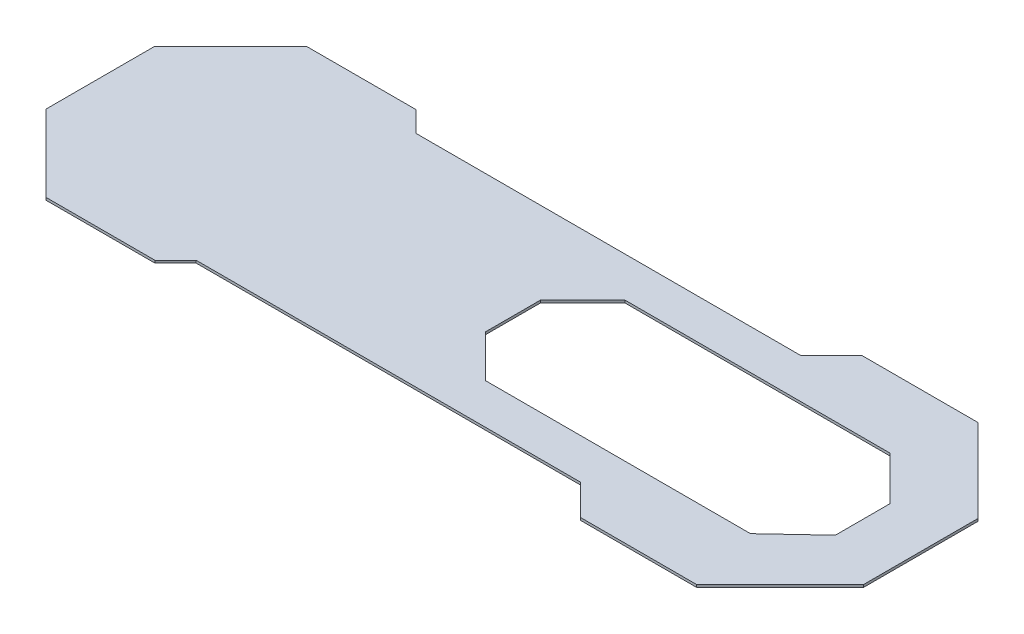
SolidWorks part; units mm, degrees
ref_plane "Спереди" through (0, 0, 0) normal (0, 0, 1) x (1, 0, 0)
ref_plane "Сверху" through (0, 0, 0) normal (0, 1, 0) x (1, 0, 0)
ref_plane "Справа" through (0, 0, 0) normal (1, 0, 0) x (0, 0, -1)
sketch "Эскиз1" plane through (0, 0, 0) normal (0, 1, 0) x (1, 0, 0)
  line L0 (-58.5138, -161.8896) -> (-212.3646, -161.8896)
  line L5 (-44.5996, -149.3896) -> (-46.0138, -149.3896)
  line L6 (0.4781, -149.3896) -> (-44.5996, -149.3896)
  line L7 (-46.0138, -149.3896) -> (-58.5138, -161.8896)
  line L8 (33.8892, -182.8008) -> (0.4781, -149.3896)
  line L10 (33.8892, -228.7785) -> (33.8892, -182.8008)
  line L12 (33.8892, -228.7785) -> (0.2781, -262.3896)
  line L14 (-44.5996, -262.3896) -> (0.2781, -262.3896)
  line L17 (-222.2788, -153.3896) -> (-220.8646, -153.3896)
  line L18 (-212.3646, -249.8896) -> (-58.5138, -249.8896)
  line L19 (-220.8646, -153.3896) -> (-212.3646, -161.8896)
  line L21 (-222.2788, -258.3896) -> (-220.8646, -258.3896)
  line L22 (-264.357, -258.3896) -> (-222.2788, -258.3896)
  line L23 (-220.8646, -258.3896) -> (-212.3646, -249.8896)
  line L24 (-295.1108, -227.6359) -> (-264.357, -258.3896)
  line L25 (-44.5996, -262.3896) -> (-46.0138, -262.3896)
  line L26 (-264.357, -153.3896) -> (-222.2788, -153.3896)
  line L27 (-46.0138, -262.3896) -> (-58.5138, -249.8896)
  line L28 (-295.1108, -184.1434) -> (-264.357, -153.3896)
  line L30 (-295.1108, -184.1434) -> (-295.1108, -227.6359)
  dimension "D3" = 225
  dimension "D4" = 225
  dimension "D5" = 135
  dimension "D6" = 225
  dimension "D11" = 135
  dimension "D12" = 135
  dimension "D13" = 135
  dimension "D14" = 135
  dimension "D15" = 45.0777
sheet metal parameters "Листовой металл1" thickness 1 parameters "D1"=1.2, "Толщина"=1
sheet metal parameters "Листовой металл2" thickness 1 parameters "D1"=1.2, "Толщина"=1
base flange "Базовая кромка1" sketch "Эскиз1" thickness 1 reverse thickness direction no parameters "D1"=1.2
sketch "Эскиз3" plane through (0, 0, 0) normal (0, 1, 0) x (1, 0, 0)
  line L0 (-129.6506, -194.8548) -> (-112.6623, -177.8665)
  line L1 (-112.6623, -177.8665) -> (-6.6329, -177.8665)
  line L2 (-6.6329, -177.8665) -> (10.8952, -195.3946)
  line L3 (10.8952, -195.3946) -> (10.8952, -217.2652)
  line L4 (10.8952, -217.2652) -> (-6.6334, -233.7128)
  line L5 (-6.6334, -233.7128) -> (-112.6624, -233.7128)
  line L6 (-112.6624, -233.7128) -> (-129.6506, -216.7245)
  line L7 (-129.6506, -216.7245) -> (-129.6506, -194.8548)
  line L18 (-129.6506, -205.7896) -> (10.8952, -205.7896) construction
  line L21 (10.8952, -205.7896) -> (33.8892, -205.7896) construction
  line L22 (33.8892, -228.7785) -> (33.8892, -182.8008) construction
  dimension "D2" = 10.9349
  dimension "D3" = 10.9349
  dimension "D4" = 225
  dimension "D5" = 135
  dimension "D6" = 225
  dimension "D7" = 135
  dimension "D8" = 10.395
  dimension "D9" = 106.0294
  dimension "D10" = 24.0251
  dimension "D11" = 21.8697
  dimension "D12" = 24.025
  dimension "D13" = 106.029
  dimension "D14" = 135
extrude "Вырез-Вытянуть1" cut sketch "Эскиз3" against normal blind 10 normal cut yes
sketch "Эскиз4" plane through (0, 0, 0) normal (0, 1, 0) x (1, 0, 0)
  line L0 (-264.2534, -153.6396) -> (-216.1257, -153.6396)
  line L1 (-264.2534, -258.1396) -> (-216.7815, -258.1396)
  line L2 (-294.8608, -227.5323) -> (-264.2534, -258.1396)
  line L3 (-294.8608, -184.247) -> (-294.8608, -227.5323)
  line L4 (-294.8608, -184.247) -> (-264.2534, -153.6396)
  line L5 (-220.8646, -153.3896) -> (-264.357, -153.3896) construction
  line L6 (-264.357, -258.3896) -> (-220.8646, -258.3896) construction
  line L7 (-295.1108, -227.6359) -> (-264.357, -258.3896) construction
  line L8 (-295.1108, -184.1434) -> (-295.1108, -227.6359) construction
  line L9 (-264.357, -153.3896) -> (-295.1108, -184.1434) construction
  line L10 (-47.513, -149.6396) -> (0.3745, -149.6396)
  line L11 (0.4781, -149.3896) -> (-46.0138, -149.3896) construction
  line L12 (-50.15, -262.1396) -> (0.1745, -262.1396)
  line L13 (-46.0138, -262.3896) -> (0.2781, -262.3896) construction
  line L14 (33.6392, -182.9043) -> (33.6392, -228.6749)
  line L15 (33.8892, -228.7785) -> (33.8892, -182.8008) construction
  line L16 (0.3745, -149.6396) -> (33.6392, -182.9043)
  line L17 (33.8892, -182.8008) -> (0.4781, -149.3896) construction
  line L18 (0.1745, -262.1396) -> (33.6392, -228.6749)
  line L19 (0.2781, -262.3896) -> (33.8892, -228.7785) construction
  line L20 (-47.513, -149.6396) -> (-47.513, -129.066)
  line L21 (-47.513, -129.066) -> (64.548, -129.066)
  line L22 (64.548, -129.066) -> (64.548, -286.8054)
  line L23 (64.548, -286.8054) -> (-50.15, -286.8054)
  line L24 (-50.15, -286.8054) -> (-50.15, -262.1396)
  line L25 (-216.1257, -153.6396) -> (-216.1257, -129.066)
  line L26 (-216.1257, -129.066) -> (-310.4871, -129.066)
  line L27 (-310.4871, -129.066) -> (-310.4871, -280.3184)
  line L28 (-310.4871, -280.3184) -> (-216.7815, -280.3184)
  line L29 (-216.7815, -280.3184) -> (-216.7815, -258.1396)
  dimension "D1" = 0.25
  dimension "D2" = 0.25
  dimension "D3" = 0.25
  dimension "D4" = 0.25
  dimension "D5" = 0.25
  dimension "D6" = 0.25
  dimension "D7" = 0.25
  dimension "D8" = 0.25
  dimension "D9" = 0.25
  dimension "D10" = 0.25
extrude "Вырез-Вытянуть2" cut sketch "Эскиз4" against normal blind 10 normal cut yes
flat pattern "Развертка1" [suppressed]
sketch "Сгиб-Линии1" plane through (0, 0, 0) normal (0, 1, 0) x (1, 0, 0)
sketch3d "Граничная рамка1" [suppressed]
  line L0 (116.8178, 58.9403, 0) -> (-182.6875, 195.0932, 0) construction
  line L1 (70.054, -43.9293, 0) -> (-229.4513, 92.2236, 0) construction
  line L2 (116.8178, 58.9403, 0) -> (70.054, -43.9293, 0) construction
  line L3 (-182.6875, 195.0932, 0) -> (-229.4513, 92.2236, 0) construction
flat pattern "Развертка2" [suppressed]
sketch "Сгиб-Линии2" plane through (0, 0, 0) normal (0, 1, 0) x (1, 0, 0)
sketch "Граничная рамка2" [suppressed] plane through (0, 0, 0) normal (0, 1, 0) x (1, 0, 0)
